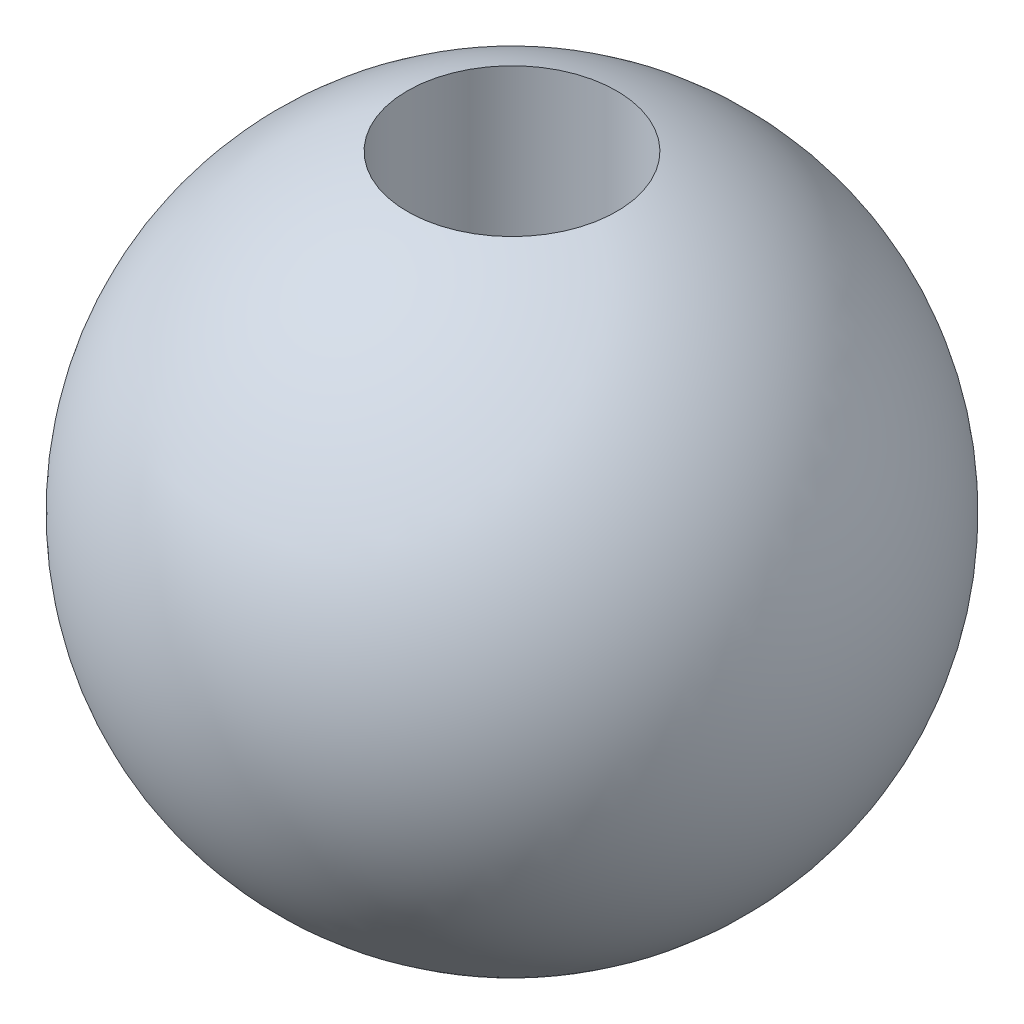
SolidWorks part; units mm, degrees
ref_plane "Front Plane" through (0, 0, 0) normal (0, 0, 1) x (1, 0, 0)
ref_plane "Top Plane" through (0, 0, 0) normal (0, 1, 0) x (1, 0, 0)
ref_plane "Right Plane" through (0, 0, 0) normal (1, 0, 0) x (0, 0, -1)
sketch "Sketch1" plane through (0, 0, 0) normal (0, 0, 1) x (1, 0, 0)
  line L0 (0, 0) -> (0, 35.3945) construction
  line L2 (-0.381, 1.1379) -> (-0.381, -1.1379)
  arc A1 (-0.381, 1.1379) -> (-0.381, -1.1379) centre (0, 0) ccw
  dimension "D1" = 0.762
  dimension "D2" = 1.2
revolve "Revolve1" add sketch "Sketch1" angle 360 about L0
sketch "Sketch2" plane through (0, 0, 0) normal (1, 0, 0) x (0, 0, -1)
  line L0 (0, 1.2) -> (0, -1.2)
  circle A0 centre (0, 0) radius 1.2 construction
  dimension "D1" = 2.4
ref_plane "Plane1" through (0, 0, 0) normal (1, 0, 0) x (0, 0, -1)
ref_plane "Plane2" through (0, 0, 0) normal (0, 1, 0) x (1, 0, 0)
ref_axis "Axis1" through (0, 1.1379, 0) along (0, -1, 0)
ref_point "Point2"
